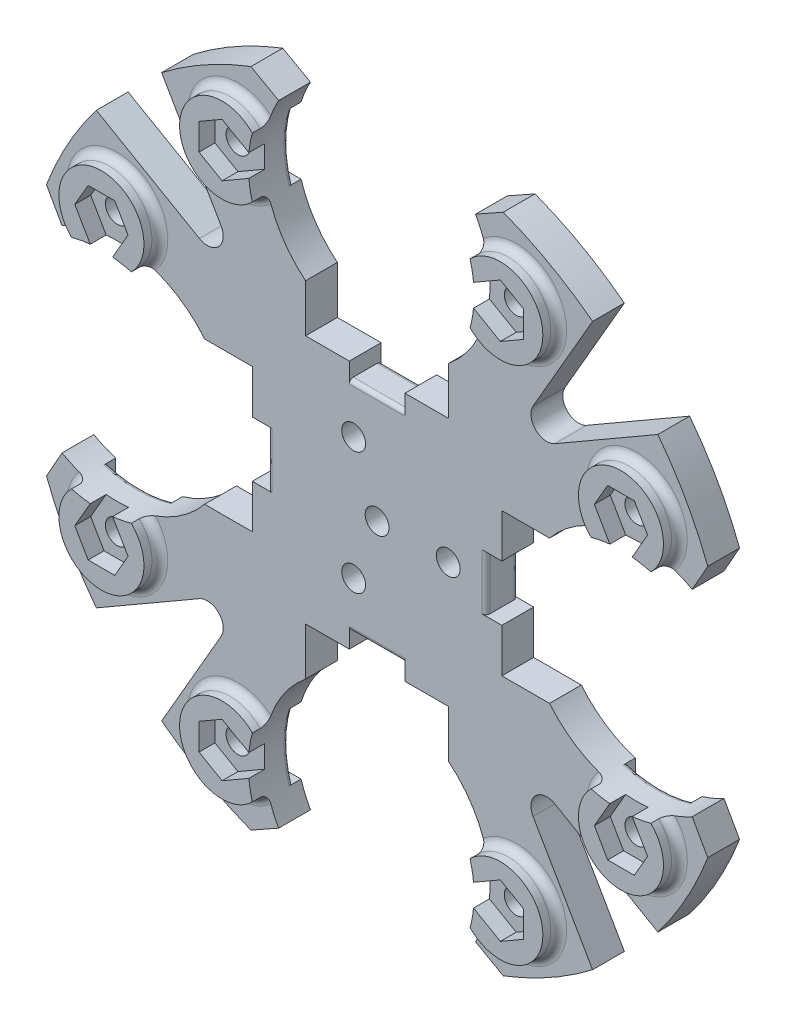
SolidWorks part; units mm, degrees
ref_plane "Front Plane" through (0, 0, 0) normal (0, 0, 1) x (1, 0, 0)
ref_plane "Top Plane" through (0, 0, 0) normal (0, 1, 0) x (1, 0, 0)
ref_plane "Right Plane" through (0, 0, 0) normal (1, 0, 0) x (0, 0, -1)
sketch "Sketch1" plane through (0, 0, 0) normal (0, 0, 1) x (1, 0, 0)
  line L4 (4.2, 14.0109) -> (4.2, 17.5)
  line L5 (-4.2, 17.5) -> (-4.2, 14.0109)
  line L6 (4.2, 13.5647) -> (4.2, 17.5)
  line L7 (-4.2, 17.5) -> (-4.2, 13.5647)
  line L10 (6.956, -12.3796) -> (15.512, -27.6067)
  line L11 (6.956, 12.3796) -> (15.512, 27.6067)
  line L12 (4.2, -17.5) -> (4.2, -14.0109)
  line L13 (-4.2, -14.0109) -> (-4.2, -17.5)
  line L14 (4.2, -17.5) -> (4.2, -13.5647)
  line L15 (-4.2, -13.5647) -> (-4.2, -17.5)
  line L16 (-10.9836, 9) -> (-16.9836, 9)
  line L17 (-10.9836, -9) -> (-16.9836, -9)
  line L18 (-16.9836, -9) -> (-16.9836, 9)
  line L19 (15.512, 27.6067) -> (3.512, 27.6067)
  line L20 (3.512, 27.6067) -> (-26.9836, 10)
  line L21 (-26.9836, 10) -> (-26.9836, -10)
  line L22 (-26.9836, -10) -> (3.512, -27.6067)
  line L23 (3.512, -27.6067) -> (15.512, -27.6067)
  line L24 (0, 0) -> (-16.9836, 0) construction
  line L25 (0, 0) -> (6.956, 12.3796) construction
  line L26 (0, 0) -> (6.956, -12.3796) construction
  line L27 (-26.9836, 0) -> (-16.9836, 0) construction
  circle A4 centre (0, 0) radius 14.2
  circle A5 centre (0, 0) radius 14.2
  arc A7 (4.2, 17.5) -> (-4.2, 17.5) centre (0, 17.5) ccw
  arc A8 (4.2, 17.5) -> (-4.2, 17.5) centre (0, 17.5) ccw
  arc A11 (-4.2, -17.5) -> (4.2, -17.5) centre (0, -17.5) ccw
  arc A12 (-4.2, -17.5) -> (4.2, -17.5) centre (0, -17.5) ccw
  dimension "D4" = 18
  dimension "D5" = 6
  dimension "D6" = 3
  dimension "D7" = 3
  dimension "D8" = 20
  dimension "D9" = 12
  dimension "D10" = 10
  dimension "D11" = 150
  dimension "D1" = 0.2
  dimension "D2" = 0.7
  dimension "D3" = 0.7
extrude "Boss-Extrude1" add sketch "Sketch1" along normal blind 3 contours A12 L15 A5 L17 L18 L16 L7 A8 L6 L11 L19 L20 L21 L22 L23 L10 L14
pattern_circular "CirPattern1" count 4 over 360 about axis through (-32.675, 0, 0) along (0, 0, 1) of "Boss-Extrude1"
sketch "Sketch2" plane through (0, 0, 0) normal (0, 0, -1) x (-1, 0, 0)
  line L6 (26.9836, 5.6914) -> (26.9836, -5.6914)
  line L7 (38.3664, 5.6914) -> (26.9836, 5.6914)
  line L8 (38.3664, -5.6914) -> (38.3664, 5.6914)
  line L9 (26.9836, -5.6914) -> (38.3664, -5.6914)
  line L10 (26.9836, 5.6914) -> (26.9836, -5.6914)
  line L11 (38.3664, 5.6914) -> (26.9836, 5.6914)
  line L12 (38.3664, -5.6914) -> (38.3664, 5.6914)
  line L13 (26.9836, -5.6914) -> (38.3664, -5.6914)
  line L53 (5.0683, 36.187) -> (16.7893, 15.8857)
  line L54 (16.7893, 15.8857) -> (-3.512, 27.6067)
  line L55 (-3.512, 27.6067) -> (-15.512, 27.6067)
  line L56 (-15.512, 27.6067) -> (-6.956, 12.3796)
  line L57 (-4.2, 13.5647) -> (-4.2, 17.5)
  line L58 (4.2, 17.5) -> (4.2, 13.5647)
  line L59 (10.9836, 9) -> (16.9836, 9)
  line L60 (16.9836, 9) -> (16.9836, -9)
  line L61 (16.9836, -9) -> (10.9836, -9)
  line L62 (4.2, -13.5647) -> (4.2, -17.5)
  line L63 (-4.2, -17.5) -> (-4.2, -13.5647)
  line L64 (-6.956, -12.3796) -> (-15.512, -27.6067)
  line L65 (-15.512, -27.6067) -> (-3.512, -27.6067)
  line L66 (-3.512, -27.6067) -> (16.7893, -15.8857)
  line L67 (16.7893, -15.8857) -> (5.0683, -36.187)
  line L68 (5.0683, -36.187) -> (5.0683, -48.187)
  line L69 (5.0683, -48.187) -> (20.2954, -39.631)
  line L70 (19.1103, -36.875) -> (15.175, -36.875)
  line L71 (15.175, -28.475) -> (19.1103, -28.475)
  line L72 (23.675, -21.6914) -> (23.675, -15.6914)
  line L73 (23.675, -15.6914) -> (41.675, -15.6914)
  line L74 (41.675, -15.6914) -> (41.675, -21.6914)
  line L75 (46.2397, -28.475) -> (50.175, -28.475)
  line L76 (50.175, -36.875) -> (46.2397, -36.875)
  line L77 (45.0546, -39.631) -> (60.2817, -48.187)
  line L78 (60.2817, -48.187) -> (60.2817, -36.187)
  line L79 (60.2817, -36.187) -> (48.5607, -15.8857)
  line L80 (48.5607, -15.8857) -> (68.862, -27.6067)
  line L81 (68.862, -27.6067) -> (80.862, -27.6067)
  line L82 (80.862, -27.6067) -> (72.306, -12.3796)
  line L83 (69.55, -13.5647) -> (69.55, -17.5)
  line L84 (61.15, -17.5) -> (61.15, -13.5647)
  line L85 (54.3664, -9) -> (48.3664, -9)
  line L86 (48.3664, -9) -> (48.3664, 9)
  line L87 (48.3664, 9) -> (54.3664, 9)
  line L88 (61.15, 13.5647) -> (61.15, 17.5)
  line L89 (69.55, 17.5) -> (69.55, 13.5647)
  line L90 (72.306, 12.3796) -> (80.862, 27.6067)
  line L91 (80.862, 27.6067) -> (68.862, 27.6067)
  line L92 (68.862, 27.6067) -> (48.5607, 15.8857)
  line L93 (48.5607, 15.8857) -> (60.2817, 36.187)
  line L94 (60.2817, 36.187) -> (60.2817, 48.187)
  line L95 (60.2817, 48.187) -> (45.0546, 39.631)
  line L96 (46.2397, 36.875) -> (50.175, 36.875)
  line L97 (50.175, 28.475) -> (46.2397, 28.475)
  line L98 (41.675, 21.6914) -> (41.675, 15.6914)
  line L99 (41.675, 15.6914) -> (23.675, 15.6914)
  line L100 (23.675, 15.6914) -> (23.675, 21.6914)
  line L101 (19.1103, 28.475) -> (15.175, 28.475)
  line L102 (15.175, 36.875) -> (19.1103, 36.875)
  line L103 (20.2954, 39.631) -> (5.0683, 48.187)
  line L104 (5.0683, 48.187) -> (5.0683, 36.187)
  line L105 (5.0683, 36.187) -> (16.7893, 15.8857)
  line L106 (16.7893, 15.8857) -> (-3.512, 27.6067)
  line L107 (-3.512, 27.6067) -> (-15.512, 27.6067)
  line L108 (-15.512, 27.6067) -> (-6.956, 12.3796)
  line L109 (-4.2, 13.5647) -> (-4.2, 17.5)
  line L110 (4.2, 17.5) -> (4.2, 13.5647)
  line L111 (10.9836, 9) -> (16.9836, 9)
  line L112 (16.9836, 9) -> (16.9836, -9)
  line L113 (16.9836, -9) -> (10.9836, -9)
  line L114 (4.2, -13.5647) -> (4.2, -17.5)
  line L115 (-4.2, -17.5) -> (-4.2, -13.5647)
  line L116 (-6.956, -12.3796) -> (-15.512, -27.6067)
  line L117 (-15.512, -27.6067) -> (-3.512, -27.6067)
  line L118 (-3.512, -27.6067) -> (16.7893, -15.8857)
  line L119 (16.7893, -15.8857) -> (5.0683, -36.187)
  line L120 (5.0683, -36.187) -> (5.0683, -48.187)
  line L121 (5.0683, -48.187) -> (20.2954, -39.631)
  line L122 (19.1103, -36.875) -> (15.175, -36.875)
  line L123 (15.175, -28.475) -> (19.1103, -28.475)
  line L124 (23.675, -21.6914) -> (23.675, -15.6914)
  line L125 (23.675, -15.6914) -> (41.675, -15.6914)
  line L126 (41.675, -15.6914) -> (41.675, -21.6914)
  line L127 (46.2397, -28.475) -> (50.175, -28.475)
  line L128 (50.175, -36.875) -> (46.2397, -36.875)
  line L129 (45.0546, -39.631) -> (60.2817, -48.187)
  line L130 (60.2817, -48.187) -> (60.2817, -36.187)
  line L131 (60.2817, -36.187) -> (48.5607, -15.8857)
  line L132 (48.5607, -15.8857) -> (68.862, -27.6067)
  line L133 (68.862, -27.6067) -> (80.862, -27.6067)
  line L134 (80.862, -27.6067) -> (72.306, -12.3796)
  line L135 (69.55, -13.5647) -> (69.55, -17.5)
  line L136 (61.15, -17.5) -> (61.15, -13.5647)
  line L137 (54.3664, -9) -> (48.3664, -9)
  line L138 (48.3664, -9) -> (48.3664, 9)
  line L139 (48.3664, 9) -> (54.3664, 9)
  line L140 (61.15, 13.5647) -> (61.15, 17.5)
  line L141 (69.55, 17.5) -> (69.55, 13.5647)
  line L142 (72.306, 12.3796) -> (80.862, 27.6067)
  line L143 (80.862, 27.6067) -> (68.862, 27.6067)
  line L144 (68.862, 27.6067) -> (48.5607, 15.8857)
  line L145 (48.5607, 15.8857) -> (60.2817, 36.187)
  line L146 (60.2817, 36.187) -> (60.2817, 48.187)
  line L147 (60.2817, 48.187) -> (45.0546, 39.631)
  line L148 (46.2397, 36.875) -> (50.175, 36.875)
  line L149 (50.175, 28.475) -> (46.2397, 28.475)
  line L150 (41.675, 21.6914) -> (41.675, 15.6914)
  line L151 (41.675, 15.6914) -> (23.675, 15.6914)
  line L152 (23.675, 15.6914) -> (23.675, 21.6914)
  line L153 (19.1103, 28.475) -> (15.175, 28.475)
  line L154 (15.175, 36.875) -> (19.1103, 36.875)
  line L155 (20.2954, 39.631) -> (5.0683, 48.187)
  line L156 (5.0683, 48.187) -> (5.0683, 36.187)
  arc A24 (-4.2, 13.5647) -> (-6.956, 12.3796) centre (0, 0) ccw
  arc A25 (4.2, 17.5) -> (-4.2, 17.5) centre (0, 17.5) ccw
  arc A26 (10.9836, 9) -> (4.2, 13.5647) centre (0, 0) ccw
  arc A27 (4.2, -13.5647) -> (10.9836, -9) centre (0, 0) ccw
  arc A28 (-4.2, -17.5) -> (4.2, -17.5) centre (0, -17.5) ccw
  arc A29 (-6.956, -12.3796) -> (-4.2, -13.5647) centre (0, 0) ccw
  arc A30 (19.1103, -36.875) -> (20.2954, -39.631) centre (32.675, -32.675) ccw
  arc A31 (15.175, -28.475) -> (15.175, -36.875) centre (15.175, -32.675) ccw
  arc A32 (23.675, -21.6914) -> (19.1103, -28.475) centre (32.675, -32.675) ccw
  arc A33 (46.2397, -28.475) -> (41.675, -21.6914) centre (32.675, -32.675) ccw
  arc A34 (50.175, -36.875) -> (50.175, -28.475) centre (50.175, -32.675) ccw
  arc A35 (45.0546, -39.631) -> (46.2397, -36.875) centre (32.675, -32.675) ccw
  arc A36 (69.55, -13.5647) -> (72.306, -12.3796) centre (65.35, 0) ccw
  arc A37 (61.15, -17.5) -> (69.55, -17.5) centre (65.35, -17.5) ccw
  arc A38 (54.3664, -9) -> (61.15, -13.5647) centre (65.35, 0) ccw
  arc A39 (61.15, 13.5647) -> (54.3664, 9) centre (65.35, 0) ccw
  arc A40 (69.55, 17.5) -> (61.15, 17.5) centre (65.35, 17.5) ccw
  arc A41 (72.306, 12.3796) -> (69.55, 13.5647) centre (65.35, 0) ccw
  arc A42 (46.2397, 36.875) -> (45.0546, 39.631) centre (32.675, 32.675) ccw
  arc A43 (50.175, 28.475) -> (50.175, 36.875) centre (50.175, 32.675) ccw
  arc A44 (41.675, 21.6914) -> (46.2397, 28.475) centre (32.675, 32.675) ccw
  arc A45 (19.1103, 28.475) -> (23.675, 21.6914) centre (32.675, 32.675) ccw
  arc A46 (15.175, 36.875) -> (15.175, 28.475) centre (15.175, 32.675) ccw
  arc A47 (20.2954, 39.631) -> (19.1103, 36.875) centre (32.675, 32.675) ccw
  arc A48 (-4.2, 13.5647) -> (-6.956, 12.3796) centre (0, 0) ccw
  arc A49 (4.2, 17.5) -> (-4.2, 17.5) centre (0, 17.5) ccw
  arc A50 (10.9836, 9) -> (4.2, 13.5647) centre (0, 0) ccw
  arc A51 (4.2, -13.5647) -> (10.9836, -9) centre (0, 0) ccw
  arc A52 (-4.2, -17.5) -> (4.2, -17.5) centre (0, -17.5) ccw
  arc A53 (-6.956, -12.3796) -> (-4.2, -13.5647) centre (0, 0) ccw
  arc A54 (19.1103, -36.875) -> (20.2954, -39.631) centre (32.675, -32.675) ccw
  arc A55 (15.175, -28.475) -> (15.175, -36.875) centre (15.175, -32.675) ccw
  arc A56 (23.675, -21.6914) -> (19.1103, -28.475) centre (32.675, -32.675) ccw
  arc A57 (46.2397, -28.475) -> (41.675, -21.6914) centre (32.675, -32.675) ccw
  arc A58 (50.175, -36.875) -> (50.175, -28.475) centre (50.175, -32.675) ccw
  arc A59 (45.0546, -39.631) -> (46.2397, -36.875) centre (32.675, -32.675) ccw
  arc A60 (69.55, -13.5647) -> (72.306, -12.3796) centre (65.35, 0) ccw
  arc A61 (61.15, -17.5) -> (69.55, -17.5) centre (65.35, -17.5) ccw
  arc A62 (54.3664, -9) -> (61.15, -13.5647) centre (65.35, 0) ccw
  arc A63 (61.15, 13.5647) -> (54.3664, 9) centre (65.35, 0) ccw
  arc A64 (69.55, 17.5) -> (61.15, 17.5) centre (65.35, 17.5) ccw
  arc A65 (72.306, 12.3796) -> (69.55, 13.5647) centre (65.35, 0) ccw
  arc A66 (46.2397, 36.875) -> (45.0546, 39.631) centre (32.675, 32.675) ccw
  arc A67 (50.175, 28.475) -> (50.175, 36.875) centre (50.175, 32.675) ccw
  arc A68 (41.675, 21.6914) -> (46.2397, 28.475) centre (32.675, 32.675) ccw
  arc A69 (19.1103, 28.475) -> (23.675, 21.6914) centre (32.675, 32.675) ccw
  arc A70 (15.175, 36.875) -> (15.175, 28.475) centre (15.175, 32.675) ccw
  arc A71 (20.2954, 39.631) -> (19.1103, 36.875) centre (32.675, 32.675) ccw
  dimension "D1" = 0
  dimension "D2" = 0
extrude "Boss-Extrude2" add sketch "Sketch2" along normal blind 1
sketch "Sketch3" plane through (0, 0, 3) normal (0, 0, 1) x (1, 0, 0)
  line L0 (4.2, 13.5647) -> (4.2, 17.5) construction
  line L1 (-4.2, 17.5) -> (-4.2, 13.5647) construction
  line L2 (4.2, 13.5647) -> (4.2, 17.5)
  line L3 (-4.2, 17.5) -> (-4.2, 13.5647)
  line L4 (-16.9836, 0) -> (39.9164, 0) construction
  line L5 (-16.9836, -9) -> (-16.9836, 9) construction
  line L6 (4.2, -13.5647) -> (4.2, -17.5)
  line L7 (-4.2, -17.5) -> (-4.2, -13.5647)
  arc A0 (6.956, 12.3796) -> (4.2, 13.5647) centre (0, 0) ccw construction
  arc A1 (4.2, 13.5647) -> (-4.2, 13.5647) centre (0, 0) ccw
  arc A2 (4.2, 17.5) -> (-4.2, 17.5) centre (0, 17.5) ccw construction
  arc A3 (4.2, 17.5) -> (-4.2, 17.5) centre (0, 17.5) ccw
  circle A4 centre (0, 17.5) radius 2 construction
  arc A5 (4.2, -13.5647) -> (-4.2, -13.5647) centre (0, 0) cw
  arc A6 (4.2, -17.5) -> (-4.2, -17.5) centre (0, -17.5) cw
  circle A7 centre (0, -17.5) radius 2 construction
  circle A8 centre (0, -17.5) radius 2 construction
  circle A9 centre (0, 17.5) radius 1.5
  circle A10 centre (0, -17.5) radius 1.5
  dimension "D1" = 4
  dimension "D2" = 3
  dimension "D3" = 3
extrude "Boss-Extrude3" add sketch "Sketch3" against normal offset from surface (3 mm away) 1 up to face at (-32.675, 0, -1)
pattern_circular "CirPattern2" count 4 over 360 about axis through (-32.675, 0, 0) along (0, 0, 1) of "Boss-Extrude3"
sketch "Sketch4" plane through (0, 0, 3) normal (0, 0, 1) x (1, 0, 0)
  line L0 (-48.3664, 9) -> (-48.3664, -9) construction
  line L1 (-50.3664, -3.5) -> (-46.3664, -3.5)
  line L2 (-50.3664, -3.5) -> (-50.3664, 3.5)
  line L3 (-50.3664, 3.5) -> (-46.3664, 3.5)
  line L4 (-46.3664, -3.5) -> (-46.3664, 3.5)
  line L5 (-50.3664, -3.5) -> (-46.3664, 3.5) construction
  line L6 (-50.3664, 3.5) -> (-46.3664, -3.5) construction
  point P0 (-48.3664, 0)
  dimension "D1" = 7
  dimension "D2" = 2
extrude "Cut-Extrude1" cut sketch "Sketch4" against normal through all
pattern_circular "CirPattern3" count 4 over 360 about axis through (-32.675, 0, 0) along (0, 0, 1) of "Cut-Extrude1"
sketch "Sketch5" plane through (0, 0, 3) normal (0, 0, 1) x (1, 0, 0)
  line L0 (-72.306, 12.3796) -> (-74.2654, 15.8668) construction
  line L1 (-72.306, 12.3796) -> (-80.862, 27.6067) construction
  circle A0 centre (-32.675, 0) radius 44.5143
  circle A1 centre (-32.675, 0) radius 64.0599
  dimension "D1" = 4
extrude "Cut-Extrude2" cut sketch "Sketch5" against normal through all
sketch "Sketch6" plane through (0, 0, 3) normal (0, 0, 1) x (1, 0, 0)
  circle A0 centre (-32.675, 0) radius 1.5
  circle A1 centre (-32.675, 0) radius 5
  dimension "D1" = 10
  dimension "D2" = 3
extrude "Boss-Extrude6" add sketch "Sketch6" against normal up to surface (4 mm away) separate body up to face at (-32.675, 0, -1)
sketch "Sketch7" plane through (0, 0, 3) normal (0, 0, 1) x (1, 0, 0)
  line L5 (-26.9836, 5.6914) -> (-38.3664, 5.6914)
  line L6 (-26.9836, -5.6914) -> (-26.9836, 5.6914)
  line L7 (-38.3664, -5.6914) -> (-26.9836, -5.6914)
  line L8 (-38.3664, 5.6914) -> (-38.3664, -5.6914)
  line L9 (-26.9836, 5.6914) -> (-38.3664, 5.6914)
  line L10 (-26.9836, -5.6914) -> (-26.9836, 5.6914)
  line L11 (-38.3664, -5.6914) -> (-26.9836, -5.6914)
  line L12 (-38.3664, 5.6914) -> (-38.3664, -5.6914)
  circle A0 centre (-32.675, 0) radius 5 construction
  circle A1 centre (-32.675, 0) radius 5
  dimension "D1" = 0
extrude "Boss-Extrude7" add sketch "Sketch7" against normal up to surface (4 mm away) up to face at (-32.675, 0, -1)
sketch "Sketch8" plane through (0, 0, -1) normal (0, 0, -1) x (-1, 0, 0)
  line L0 (26.425, 11) -> (20.425, 2.5)
  line L1 (26.425, 11) -> (38.925, 11)
  line L2 (26.425, 11) -> (26.425, -11) construction
  line L3 (26.425, -11) -> (38.925, -11)
  line L4 (38.925, 11) -> (38.925, -11)
  line L5 (26.425, 11) -> (38.925, -11) construction
  line L6 (26.425, -11) -> (38.925, 11) construction
  line L7 (20.425, 2.5) -> (20.425, -2.5)
  line L8 (20.425, -2.5) -> (26.425, -11)
  line L9 (20.425, 0) -> (32.675, 0) construction
  circle A0 centre (32.675, 0) radius 5.25 construction
  point P0 (32.675, 0)
  dimension "D1" = 1
  dimension "D2" = 22
  dimension "D3" = 6
  dimension "D4" = 5
extrude "Cut-Extrude3" cut sketch "Sketch8" against normal blind 1
sketch "Sketch9" plane through (0, 0, -1) normal (0, 0, -1) x (-1, 0, 0)
  circle A0 centre (35.625, 7.7) radius 1.5 construction
  circle A1 centre (35.625, -7.7) radius 1.5 construction
  circle A2 centre (23.725, 0) radius 1.5 construction
  circle A3 centre (35.625, 7.7) radius 1.5
  circle A4 centre (35.625, -7.7) radius 1.5
  circle A5 centre (23.725, 0) radius 1.5
extrude "Cut-Extrude4" cut sketch "Sketch9" against normal blind 24
fillet "Fillet1" radius 2 4 edges at (-48.5607, 15.8857, 1) (-48.5607, -15.8857, 1) (-16.7893, -15.8857, 1) (-16.7893, 15.8857, 1)
fillet "Fillet2" radius 0.5 8 edges at (0, 14.2, 0) (0, -14.2, 0) (-46.875, 32.675, 0) (-18.475, 32.675, 0) (-65.35, -14.2, 0) (-65.35, 14.2, 0) (-18.475, -32.675, 0) (-46.875, -32.675, 0)
sketch "Sketch10" plane through (0, 0, 3) normal (0, 0, 1) x (1, 0, 0)
  line L0 (-47.275, 32.675) -> (-32.675, 32.675) construction
  line L1 (-47.275, 31.0007) -> (-47.275, 34.3493) construction
  line L2 (-47.275, 34.3493) -> (-50.175, 36.0236)
  line L3 (-50.175, 36.0236) -> (-53.075, 34.3493)
  line L4 (-53.075, 34.3493) -> (-53.075, 31.0007)
  line L5 (-53.075, 31.0007) -> (-50.175, 29.3264)
  line L6 (-50.175, 29.3264) -> (-47.275, 31.0007)
  line L7 (-47.275, 34.3493) -> (-44.375, 32.675)
  line L8 (-44.375, 32.675) -> (-47.275, 31.0007)
  line L9 (-32.675, 32.675) -> (-32.675, 43.795) construction
  line L10 (-18.075, 34.3493) -> (-15.175, 36.0236)
  line L11 (-18.075, 34.3493) -> (-20.975, 32.675)
  line L12 (-20.975, 32.675) -> (-18.075, 31.0007)
  line L13 (-15.175, 29.3264) -> (-18.075, 31.0007)
  line L14 (-12.275, 31.0007) -> (-15.175, 29.3264)
  line L15 (-12.275, 34.3493) -> (-12.275, 31.0007)
  line L16 (-15.175, 36.0236) -> (-12.275, 34.3493)
  circle A0 centre (-50.175, 32.675) radius 2.9 construction
  arc A1 (-45.0546, 39.631) -> (-41.675, 21.6914) centre (-32.675, 32.675) ccw construction
  arc A2 (-45.0546, 39.631) -> (-41.675, 21.6914) centre (-32.675, 32.675) ccw
  circle A3 centre (-50.175, 32.675) radius 5.3486
  arc A4 (-20.2954, 39.631) -> (-23.675, 21.6914) centre (-32.675, 32.675) cw
  circle A5 centre (-15.175, 32.675) radius 5.3486
  dimension "D1" = 5.8
  dimension "D2" = 2
extrude "Boss-Extrude8" add sketch "Sketch10" along normal blind 2 contours A2 A3 L8 L6 L5 L4 L3 L2 L7 | A5 A4 L11 L10 L16 L15 L14 L13 L12
pattern_circular "CirPattern4" count 4 over 360 about axis through (-32.675, 0, 0) along (0, 0, 1) of "Boss-Extrude8"
fillet "Fillet3" radius 1 8 edges at (-9.8264, 32.675, 3) (-65.35, -22.8486, 3) (-65.35, 22.8486, 3) (-9.8264, -32.675, 3) (-55.5236, -32.675, 3) (0, 22.8486, 3) (0, -22.8486, 3) (-55.5236, 32.675, 3)
fillet "Fillet4" radius 0.5 8 edges at (-46.3664, 0, 3) (-46.3664, 0, -1) (-32.675, -13.6914, 3) (-32.675, -13.6914, -1) (-18.9836, 0, 3) (-18.9836, 0, -1) (-32.675, 13.6914, 3) (-32.675, 13.6914, -1)
sketch "Sketch13" plane through (0, 0, 0) normal (0, 0, -1) x (-1, 0, 0)
  line L0 (0, 0) -> (-28.6177, 0) construction
  circle A0 centre (0, -17.5) radius 1.9
  circle A1 centre (0, -17.5) radius 1.5 construction
  circle A2 centre (0, -17.5) radius 1.5
  circle A3 centre (0, 17.5) radius 1.5
  circle A4 centre (0, 17.5) radius 1.9
  dimension "D1" = 3.8
extrude "Boss-Extrude10" add sketch "Sketch13" along normal up to surface (1 mm away) up to face at (-28.5917, 0, -1)
pattern_circular "CirPattern5" count 4 over 360 about axis through (-32.675, 0, 0) along (0, 0, 1) of "Boss-Extrude10"
sketch "Sketch14" plane through (0, 0, 0) normal (0, 0, -1) x (-1, 0, 0)
  circle A0 centre (35.625, 7.7) radius 1.5 construction
  circle A1 centre (35.625, -7.7) radius 1.5 construction
  circle A2 centre (32.675, 0) radius 1.5 construction
  circle A3 centre (23.725, 0) radius 1.5 construction
  circle A4 centre (35.625, 7.7) radius 1.5
  circle A5 centre (35.625, -7.7) radius 1.5
  circle A6 centre (32.675, 0) radius 1.5
  circle A7 centre (23.725, 0) radius 1.5
  circle A8 centre (35.625, 7.7) radius 1.9
  circle A9 centre (35.625, -7.7) radius 1.9
  circle A10 centre (32.675, 0) radius 1.9
  circle A11 centre (23.725, 0) radius 1.9
  dimension "D1" = 0.4
extrude "Boss-Extrude11" add sketch "Sketch14" along normal up to surface (1 mm away) up to face at (-28.5917, 0, -1)
